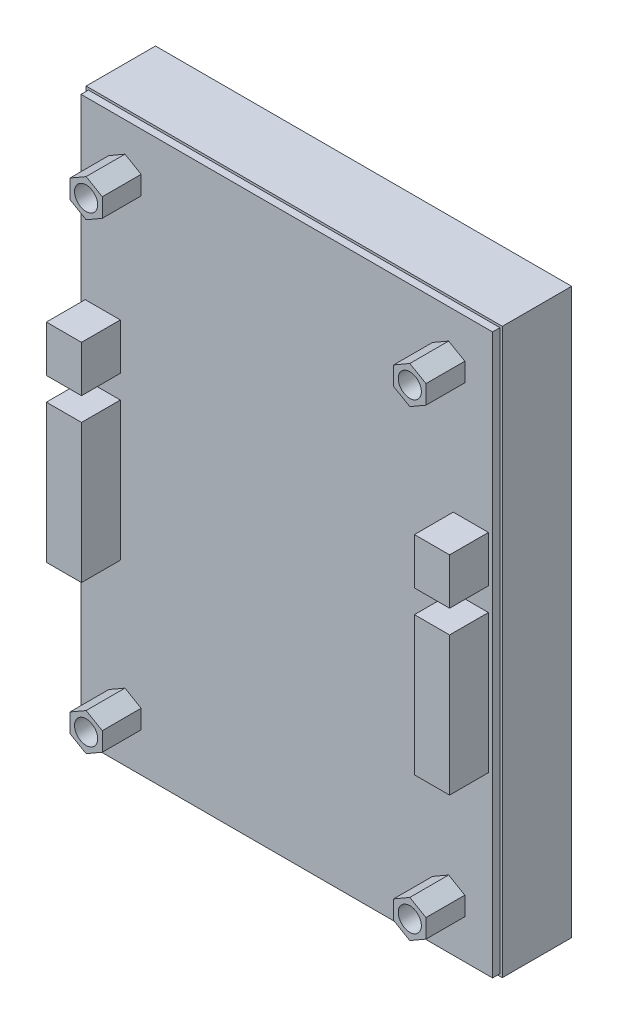
SolidWorks part; units mm, degrees
material "ABS"
ref_plane "Front Plane" through (0, 0, 0) normal (0, 0, 1) x (1, 0, 0)
ref_plane "Top Plane" through (0, 0, 0) normal (0, 1, 0) x (1, 0, 0)
ref_plane "Right Plane" through (0, 0, 0) normal (1, 0, 0) x (0, 0, -1)
sketch "Model" plane through (0, 0, 0) normal (0, 0, 1) x (1, 0, 0)
  line L0 (-45, 61) -> (45, 61)
  line L1 (45, 61) -> (45, -61)
  line L2 (45, -61) -> (-45, -61)
  line L3 (-45, -61) -> (-45, 61)
  line L4 (44.5, -60.5) -> (-44.5, -60.5)
  line L5 (-44.5, -60.5) -> (-44.5, 60.5)
  line L6 (-44.5, 60.5) -> (44.5, 60.5)
  line L7 (44.5, 60.5) -> (44.5, -60.5)
  line L8 (-43.6, 22.5) -> (-36, 22.5)
  line L9 (-36, 22.5) -> (-36, 12.5)
  line L10 (-36, 12.5) -> (-43.6, 12.5)
  line L11 (-43.6, 12.5) -> (-43.6, 22.5)
  line L12 (-43.6, 7.5) -> (-36, 7.5)
  line L13 (-36, 7.5) -> (-36, -22.5)
  line L14 (-36, -22.5) -> (-43.6, -22.5)
  line L15 (-43.6, -22.5) -> (-43.6, 7.5)
  line L16 (36, 22.5) -> (43.6, 22.5)
  line L17 (43.6, 22.5) -> (43.6, 12.5)
  line L18 (43.6, 12.5) -> (36, 12.5)
  line L19 (36, 12.5) -> (36, 22.5)
  line L20 (36, 7.5) -> (43.6, 7.5)
  line L21 (43.6, 7.5) -> (43.6, -22.5)
  line L22 (43.6, -22.5) -> (36, -22.5)
  line L23 (36, -22.5) -> (36, 7.5)
  line L24 (0, 61) -> (0, -61) construction
  line L25 (45, 0) -> (-45, 0) construction
  line L26 (-35, 50) -> (-35, 45.5) construction
  line L27 (-35, 50) -> (-35, 54.5) construction
  line L28 (-35, 50) -> (-30.5, 50) construction
  line L29 (-35, 50) -> (-39.5, 50) construction
  line L30 (35, 50) -> (35, 45.5) construction
  line L31 (35, 50) -> (35, 54.5) construction
  line L32 (35, 50) -> (39.5, 50) construction
  line L33 (35, 50) -> (30.5, 50) construction
  line L34 (-35, -50) -> (-35, -45.5) construction
  line L35 (-35, -50) -> (-35, -54.5) construction
  line L36 (-35, -50) -> (-39.5, -50) construction
  line L37 (-35, -50) -> (-30.5, -50) construction
  line L38 (35, -50) -> (35, -45.5) construction
  line L39 (35, -50) -> (35, -54.5) construction
  line L40 (35, -50) -> (30.5, -50) construction
  line L41 (35, -50) -> (39.5, -50) construction
  line L43 (-35, 45.9585) -> (-31.5, 47.9793)
  line L44 (-31.5, 47.9793) -> (-31.5, 52.0207)
  line L45 (-31.5, 52.0207) -> (-35, 54.0415)
  line L46 (-35, 54.0415) -> (-38.5, 52.0207)
  line L47 (-38.5, 52.0207) -> (-38.5, 47.9793)
  line L48 (-38.5, 47.9793) -> (-35, 45.9585)
  line L49 (35, 45.9585) -> (38.5, 47.9793)
  line L50 (38.5, 47.9793) -> (38.5, 52.0207)
  line L51 (38.5, 52.0207) -> (35, 54.0415)
  line L52 (35, 54.0415) -> (31.5, 52.0207)
  line L53 (31.5, 52.0207) -> (31.5, 47.9793)
  line L54 (31.5, 47.9793) -> (35, 45.9585)
  line L55 (35, -45.9585) -> (31.5, -47.9793)
  line L56 (31.5, -47.9793) -> (31.5, -52.0207)
  line L57 (31.5, -52.0207) -> (35, -54.0415)
  line L58 (35, -54.0415) -> (38.5, -52.0207)
  line L59 (38.5, -52.0207) -> (38.5, -47.9793)
  line L60 (38.5, -47.9793) -> (35, -45.9585)
  line L61 (-35, -45.9585) -> (-38.5, -47.9793)
  line L62 (-38.5, -47.9793) -> (-38.5, -52.0207)
  line L63 (-38.5, -52.0207) -> (-35, -54.0415)
  line L64 (-35, -54.0415) -> (-31.5, -52.0207)
  line L65 (-31.5, -52.0207) -> (-31.5, -47.9793)
  line L66 (-31.5, -47.9793) -> (-35, -45.9585)
  circle A0 centre (-35, 50) radius 2.5
  circle A1 centre (35, 50) radius 2.5
  circle A2 centre (-35, -50) radius 2.5
  circle A3 centre (35, -50) radius 2.5
  circle A4 centre (-35, 50) radius 3.5 construction
  circle A5 centre (35, 50) radius 3.5 construction
  circle A6 centre (35, -50) radius 3.5 construction
  circle A7 centre (-35, -50) radius 3.5 construction
  dimension "D3" = 7
  dimension "D4" = 7
  dimension "D5" = 7
  dimension "D6" = 7
  dimension "D7" = 5
  dimension "D8" = 5
  dimension "D9" = 5
  dimension "D10" = 5
  dimension "D1" = 122
  dimension "D2" = 90
extrude "Boss-Extrude1" add sketch "Model" against normal blind 15 contours L0 L1 L2 L3
extrude "Boss-Extrude2" add sketch "Model<3>" along normal blind 1.6 contours L6 L7 L4 L5
sketch "Model<3>" plane through (0, 0, 0) normal (0, 0, 1) x (1, 0, 0) same geometry as "Model"
extrude "Boss-Extrude3" add sketch "Model<4>" along normal blind 10 contours L44 L45 L46 L47 L48 L43 | L50 L51 L52 L53 L54 L49 | L59 L60 L55 L56 L57 L58 | L65 L66 L61 L62 L63 L64
sketch "Model<4>" plane through (0, 0, 0) normal (0, 0, 1) x (1, 0, 0) same geometry as "Model"
extrude "Boss-Extrude4" add sketch "Model<5>" along normal blind 10 contours L9 L10 L11 L8 | L19 L16 L17 L18
sketch "Model<5>" plane through (0, 0, 0) normal (0, 0, 1) x (1, 0, 0) same geometry as "Model"
extrude "Boss-Extrude5" add sketch "Model<6>" along normal blind 10 contours L13 L14 L15 L12 | L23 L20 L21 L22
sketch "Model<6>" plane through (0, 0, 0) normal (0, 0, 1) x (1, 0, 0) same geometry as "Model"
extrude "Cut-Extrude1" cut sketch "Model<7>" along normal blind 10 contours A2 | A3 | A1 | A0
sketch "Model<7>" plane through (0, 0, 0) normal (0, 0, 1) x (1, 0, 0) same geometry as "Model"
sketch "Sketch4" plane through (0, 0, -15) normal (0, 0, -1) x (-1, 0, 0)
  line L0 (25.369, 0.0335) -> (19.9902, 4.7816)
  line L1 (-37.1536, -42.7978) -> (-36.13, -44.9525)
  line L50 (0, 0) -> (0, 66.0932) construction
  line L51 (-19.7654, 5.9353) -> (-12.654, 40.0812)
  line L52 (-25.7696, 1.5615) -> (-19.7654, 5.9353)
  line L53 (-29.0226, 3.5604) -> (-25.7696, 1.5615)
  line L54 (-21.3914, 41.5476) -> (-29.0226, 3.5604)
  line L55 (-20.8906, 43.5466) -> (-21.3914, 41.5476)
  line L56 (-20.0154, 45.2958) -> (-20.8906, 43.5466)
  line L57 (-18.8893, 46.9206) -> (-20.0154, 45.2958)
  line L58 (-17.3886, 48.2956) -> (-18.8893, 46.9206)
  line L59 (-12.654, 40.0812) -> (-17.3886, 48.2956)
  line L60 (-10.7582, 40.4232) -> (26.2696, 40.4232)
  line L61 (-15.8871, 49.1702) -> (-10.7582, 40.4232)
  line L62 (-13.5104, 49.9194) -> (-15.8871, 49.1702)
  line L63 (-11.259, 50.0448) -> (-13.5104, 49.9194)
  line L64 (28.271, 50.0448) -> (-11.259, 50.0448)
  line L65 (28.271, 50.0448) -> (31.0232, 48.9196)
  line L66 (33.6508, 47.2956) -> (31.0232, 48.9196)
  line L67 (26.2696, 40.4232) -> (33.6508, 47.2956)
  line L68 (22.3922, 6.4348) -> (27.3956, 2.061)
  line L69 (29.1472, 40.4232) -> (22.3922, 6.4348)
  line L70 (34.9014, 45.9206) -> (29.1472, 40.4232)
  line L71 (36.152, 44.1714) -> (34.9014, 45.9206)
  line L72 (37.2782, 42.4222) -> (36.152, 44.1714)
  line L73 (38.0135, 40.4639) -> (37.2782, 42.4222)
  line L74 (38.0135, 40.4639) -> (31.5238, 4.8101)
  line L75 (27.3956, 2.061) -> (31.5238, 4.8101)
  line L76 (20.14, -6.9356) -> (13.3477, -39.4168)
  line L77 (27.771, -1.937) -> (20.14, -6.9356)
  line L78 (29.647, -3.5617) -> (27.771, -1.937)
  line L79 (21.016, -44.298) -> (29.647, -3.5617)
  line L80 (18.3604, -47.3956) -> (21.016, -44.298)
  line L81 (18.3604, -47.3956) -> (13.3477, -39.4168)
  line L82 (12.7596, -49.5456) -> (-30.2732, -49.5456)
  line L83 (19.1392, -4.0613) -> (-19.0147, -4.0613)
  line L84 (25.369, 0.0335) -> (19.1392, -4.0613)
  line L86 (-17.1378, 4.8101) -> (19.9902, 4.7816)
  line L87 (-23.6203, 0.0312) -> (-17.1378, 4.8101)
  line L88 (-19.0147, -4.0613) -> (-23.6203, 0.0312)
  line L89 (-26.7704, -1.1876) -> (-30.8986, -4.3118)
  line L90 (-22.2668, -5.0611) -> (-26.7704, -1.1876)
  line L91 (-29.1472, -39.6744) -> (-22.2668, -5.0611)
  line L92 (-36.13, -44.9525) -> (-29.1472, -39.6744)
  line L93 (-38.029, -40.7988) -> (-30.8986, -4.3118)
  line L94 (-37.1536, -42.7978) -> (-38.029, -40.7988)
  line L96 (16.652, -48.4566) -> (12.7596, -49.5456)
  line L97 (11.8843, -40.7988) -> (16.652, -48.4566)
  line L98 (-26.2704, -40.8369) -> (11.8843, -40.7988)
  line L99 (-34.276, -47.0464) -> (-26.2704, -40.8369)
  line L100 (-30.2732, -49.5456) -> (-34.276, -47.0464)
  circle A2 centre (44.5, -60.5) radius 3.0029
  circle A3 centre (31.0232, -47.0464) radius 4.9558
extrude "Cut-Extrude2" cut sketch "Sketch4" against normal blind 2 contours L51 L59 L58 L57 L56 L55 L54 L53 L52 | L60 L50 L64 L63 L62 L61 | L50 L60 L67 L66 L65 L64 | L68 L75 L74 L73 L72 L71 L70 L69 | L50 L83 L84 L0 L86 | L94 L1 L92 L91 L90 L89 L93 | L50 L82 L96 L97 L98 | L81 L80 L79 L78 L77 L76 | L82 L50 L98 L99 L100 | L83 L50 L86 L87 L88 | A3 region at (-0.8211, 0.3353, -15) region at (6.7902, 45.5165, -15) region at (-15.2324, 45.3635, -15) region at (30.2108, -22.7, -15) region at (20.586, 24.2006, -15) region at (-30.4023, 23.4053, -15) region at (-21.1605, -23.988, -15) region at (8.2787, -45.3443, -15) region at (-31.0232, -47.0464, -15)
